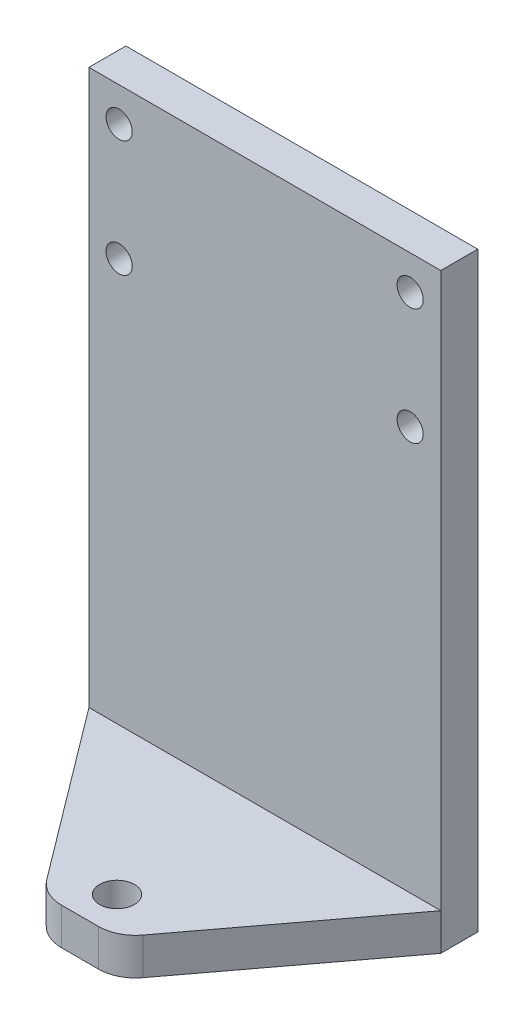
SolidWorks part; units mm, degrees
material "6061 Alloy"
ref_plane "Front" through (0, 0, 0) normal (0, 0, 1) x (1, 0, 0)
ref_plane "Top" through (0, 0, 0) normal (0, 1, 0) x (1, 0, 0)
ref_plane "Right" through (0, 0, 0) normal (1, 0, 0) x (0, 0, -1)
sketch "Sketch1" plane through (0, 0, 0) normal (0, 0, 1) x (1, 0, 0)
  line L1 (-30.226, -50.8) -> (30.226, -50.8)
  line L2 (-30.226, -50.8) -> (-30.226, 50.8)
  line L3 (-30.226, 50.8) -> (30.226, 50.8)
  line L4 (30.226, -50.8) -> (30.226, 50.8)
  line L5 (-30.226, -50.8) -> (30.226, 50.8) construction
  line L6 (-30.226, 50.8) -> (30.226, -50.8) construction
  point P0 (0, 0)
  dimension "D1" = 60.452
  dimension "D2" = 101.6
extrude "Boss-Extrude1" add sketch "Sketch1" along normal mid plane 6.35
sketch "Sketch2" plane through (0, -50.8, 0) normal (0, -1, 0) x (1, 0, 0)
  line L0 (-30.226, 3.175) -> (30.226, 3.175) construction
  line L1 (-30.226, -3.175) -> (30.226, -3.175)
  line L2 (-30.226, -3.175) -> (-30.226, 53.975)
  line L3 (-30.226, 53.975) -> (30.226, 53.975)
  line L4 (30.226, -3.175) -> (30.226, 53.975)
  dimension "D1" = 50.8
extrude "Boss-Extrude2" add sketch "Sketch2" against normal blind 6.35
sketch "Sketch3" plane through (0, 0, -3.175) normal (0, 0, -1) x (-1, 0, 0)
  circle A0 centre (-24.9644, 44.925) radius 2.25 construction
  circle A1 centre (-24.9644, 24.925) radius 2.25 construction
  circle A2 centre (25.0356, 24.925) radius 2.25 construction
  circle A3 centre (25.0356, 44.925) radius 2.25 construction
  circle A4 centre (-24.9644, 44.925) radius 2.25
  circle A5 centre (-24.9644, 24.925) radius 2.25
  circle A6 centre (25.0356, 24.925) radius 2.25
  circle A7 centre (25.0356, 44.925) radius 2.25
extrude "Cut-Extrude1" cut sketch "Sketch3" against normal through all
sketch "Sketch4" plane through (0, -44.45, 0) normal (0, 1, 0) x (1, 0, 0)
  line L0 (-30.226, -53.975) -> (-30.226, -3.175) construction
  line L1 (30.226, -53.975) -> (-30.226, -53.975) construction
  circle A0 centre (0, -28.575) radius 3
  point P4 (-30.226, -28.575)
  point P7 (0, -53.975)
  dimension "D1" = 6
extrude "Cut-Extrude2" cut sketch "Sketch4" against normal through all
sketch "Sketch5" plane through (0, -44.45, 0) normal (0, 1, 0) x (1, 0, 0)
  line L0 (-30.226, -3.175) -> (-6.35, -34.925)
  line L1 (-6.35, -34.925) -> (6.35, -34.925)
  line L2 (6.35, -34.925) -> (30.226, -3.175)
  line L3 (30.226, -3.175) -> (30.226, -53.975)
  line L4 (30.226, -53.975) -> (-30.226, -53.975)
  line L5 (-30.226, -53.975) -> (-30.226, -3.175)
  line L6 (0, -34.925) -> (0, -53.975) construction
  circle A0 centre (0, -28.575) radius 3 construction
  dimension "D1" = 6.35
  dimension "D2" = 12.7
extrude "Cut-Extrude3" cut sketch "Sketch5" against normal through all
fillet "Fillet1" radius 6.35 2 edges at (6.35, -47.625, 34.925) (-6.35, -47.625, 34.925)
